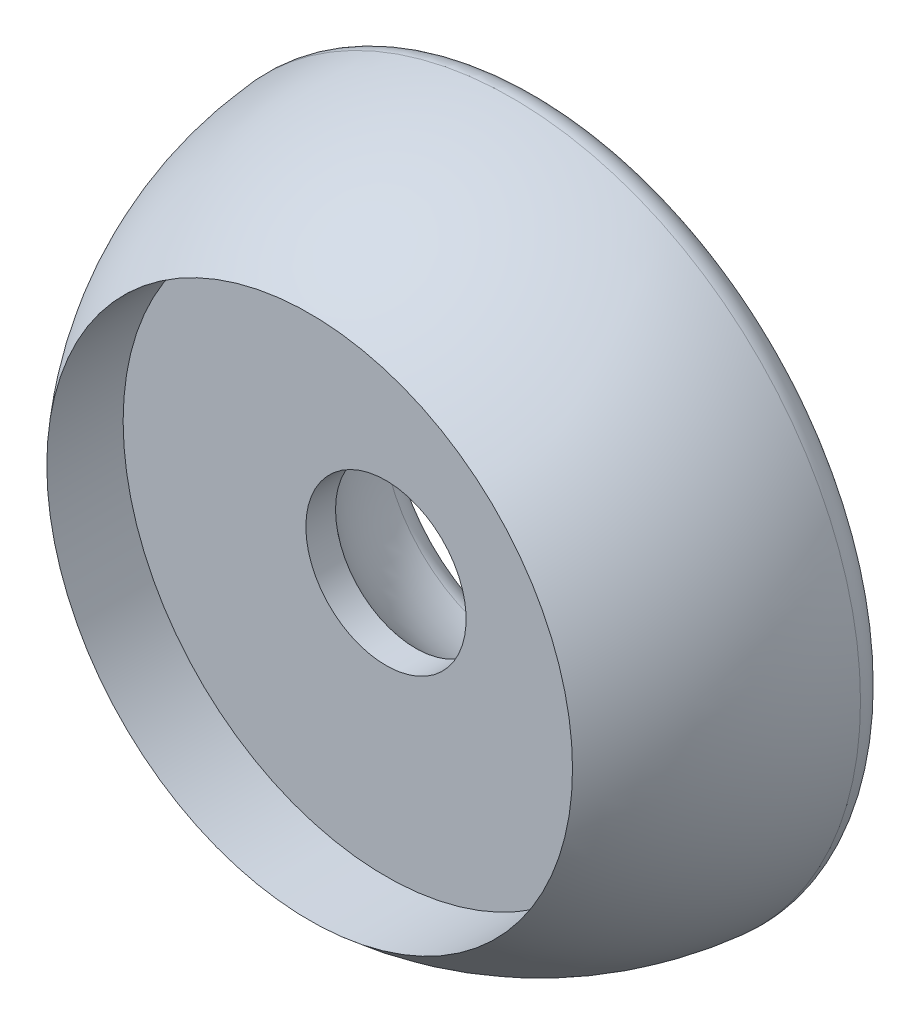
SolidWorks part; units mm, degrees
ref_plane "Front Plane" through (0, 0, 0) normal (0, 0, 1) x (1, 0, 0)
ref_plane "Top Plane" through (0, 0, 0) normal (0, 1, 0) x (1, 0, 0)
ref_plane "Right Plane" through (0, 0, 0) normal (1, 0, 0) x (0, 0, -1)
ref_axis "Polar Axis" through (0, 0, -14.3) along (0, 0, 1)
ref_axis "Solar Axis" through (-14.3, 0, 0) along (1, 0, 0)
sketch "Sketch2" plane through (0, 0, 0) normal (0, 1, 0) x (1, 0, 0)
  line L0 (2.1, 0) -> (5.45, 0)
  line L1 (1.25, -2.4) -> (4.1, -2.4)
  line L3 (4.1, -2.4) -> (4.1, -3.5906)
  line L4 (1.25, -2.4) -> (1.25, -1.9371)
  line L5 (2.1, -0.2) -> (2.1, 0)
  line L7 (0, 0) -> (0, -7) construction
  circle A0 centre (0, 0) radius 2 construction
  arc A1 (4.1, -3.5906) -> (5.45, 0) centre (0, 0) ccw
  arc A2 (1.25, -1.9371) -> (2.1, -0.2) centre (-0.1, -0.2) ccw
  dimension "D1" = 7
  dimension "D2" = 1.25
  dimension "D3" = 2.1
  dimension "D4" = 10.9
  dimension "D7" = 2.2
  dimension "D8" = 0.2
  dimension "D9" = 4
  dimension "D5" = 4.1
  dimension "D6" = 2.4
revolve "Main Body" add sketch "Sketch2" angle 360 about L7
fillet "Bottom Fillet" radius 0.4 2 edges at (-5.45, 0, 0) (-2.1, 0, 0)
